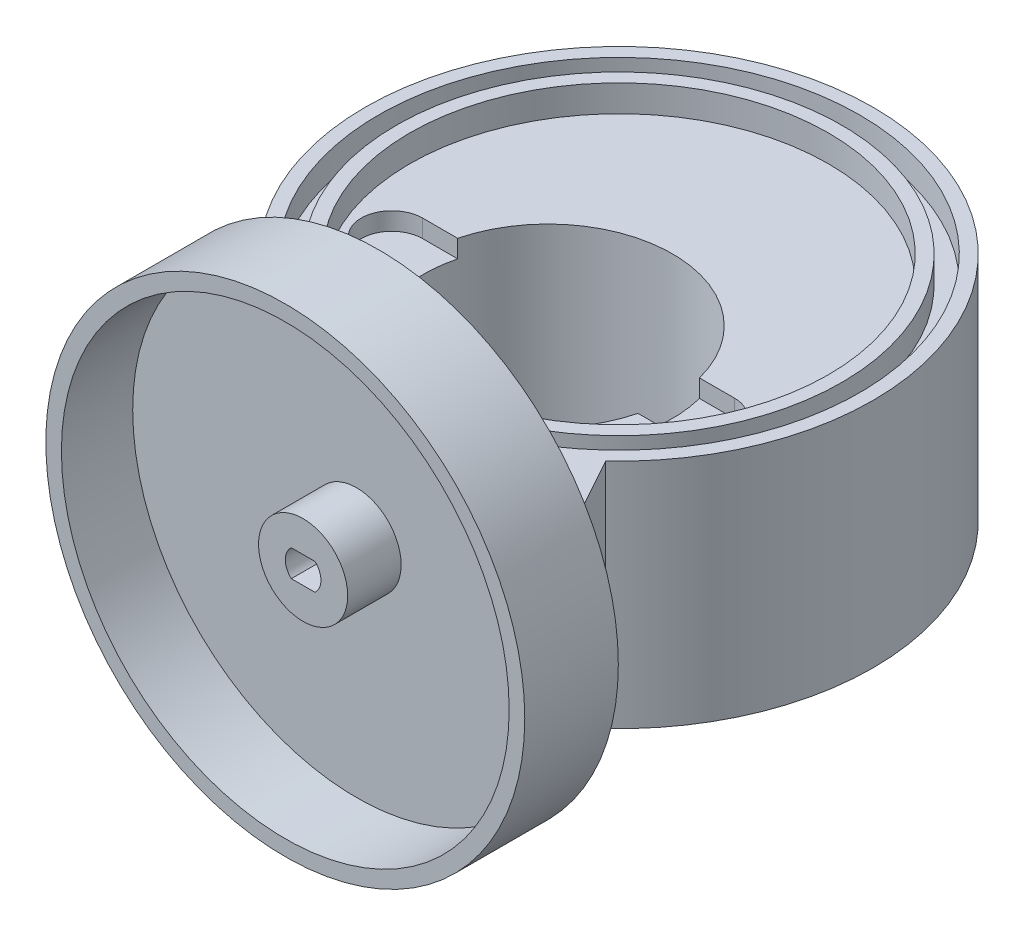
SolidWorks part; units mm, degrees
material "Custom Plastic"
ref_plane "Front Plane" through (0, 0, 0) normal (0, 0, 1) x (1, 0, 0)
ref_plane "Top Plane" through (0, 0, 0) normal (0, 1, 0) x (1, 0, 0)
ref_plane "Right Plane" through (0, 0, 0) normal (1, 0, 0) x (0, 0, -1)
sketch "Sketch1" plane through (0, 0, 0) normal (0, 1, 0) x (1, 0, 0)
  circle A0 centre (0, 0) radius 28.5
  dimension "D1" = 57
extrude "Boss-Extrude1" add sketch "Sketch1" along normal blind 3
sketch "Sketch2" plane through (0, 3, 0) normal (0, 1, 0) x (1, 0, 0)
  line L11 (0, 0) -> (0, -8) construction
  line L16 (-9, -18.7238) -> (-9, -20.2238)
  line L17 (-9, -20.2238) -> (-7.35, -22)
  line L18 (-7.35, -22) -> (-7.6173, -27.4632)
  line L20 (7.6173, -27.4632) -> (7.35, -22)
  line L21 (7.35, -22) -> (9, -20.2238)
  line L22 (9, -20.2238) -> (9, -18.7238)
  circle A9 centre (0, 0) radius 28.5 construction
  arc A10 (9, -18.7238) -> (13.5683, -11.45) centre (0, -8) ccw
  arc A12 (13.5683, -4.55) -> (-13.5683, -4.55) centre (0, -8) ccw
  arc A14 (-13.5683, -11.45) -> (-9, -18.7238) centre (0, -8) ccw
  arc A16 (-13.5683, -4.55) -> (-13.5683, -11.45) centre (0, -8) ccw
  arc A17 (13.5683, -4.55) -> (13.5683, -11.45) centre (0, -8) cw
  circle A18 centre (0, 0) radius 28.5
  circle M19 centre (0, 0) radius 28.5
  dimension "D2" = 57
  dimension "D1" = 8
extrude "Boss-Extrude4" add sketch "Sketch2" along normal blind 20 contours A12 A17 A10 L22 L21 L20 L18 L17 L16 A14 A16 M19 region at (-9.7988, 3, 19.4738)
sketch "Sketch5" plane through (0, 23, 0) normal (0, 1, 0) x (1, 0, 0)
  circle A0 centre (0, 0) radius 28.5
  circle A1 centre (0, 0) radius 23.5
  circle A2 centre (0, 0) radius 25
  circle A3 centre (0, 0) radius 27
  line M3 (9, -20.2238) -> (7.35, -22)
  line M4 (7.35, -22) -> (7.6173, -27.4632)
  arc M5 (7.6173, -27.4632) -> (-7.6173, -27.4632) centre (0, 0) ccw
  line M6 (-7.6173, -27.4632) -> (-7.35, -22)
  line M7 (-7.35, -22) -> (-9, -20.2238)
  dimension "D1" = 47
  dimension "D2" = 57
  dimension "D3" = 50
  dimension "D4" = 54
extrude "Boss-Extrude7" add sketch "Sketch5" along normal blind 3 contours A2 A1 M4 M6 M7 M3 | A3 M4 M5 M6 region at (22.0505, 23, 16.767) region at (-14.4007, 23, -19.5743)
sketch "Sketch7" plane through (0, 0, 0) normal (0, -1, 0) x (1, 0, 0)
  circle A0 centre (0, 0) radius 28.5
  circle A1 centre (0, 0) radius 23.5
  circle A2 centre (0, 0) radius 25
  circle A3 centre (0, 0) radius 27
extrude "Cut-Extrude1" cut sketch "Sketch7" against normal blind 3 contours A3 A2 region at (-26.2363, 0, 0)
sketch "Sketch8" plane through (0, 3, 0) normal (0, 1, 0) x (1, 0, 0)
  line L6 (-7.542, -25.9252) -> (-7.6173, -27.4632)
  line L7 (7.6173, -27.4632) -> (7.542, -25.9252)
  line L8 (-7.542, -25.9252) -> (-7.6173, -27.4632)
  line L9 (7.6173, -27.4632) -> (7.542, -25.9252)
  arc A2 (-7.542, -25.9252) -> (7.542, -25.9252) centre (0, 0) ccw
  arc A3 (-7.6173, -27.4632) -> (7.6173, -27.4632) centre (0, 0) ccw
  arc A4 (-7.542, -25.9252) -> (7.542, -25.9252) centre (0, 0) ccw
  arc A5 (-7.6173, -27.4632) -> (7.6173, -27.4632) centre (0, 0) ccw
  dimension "D1" = 0
extrude "Cut-Extrude2" cut sketch "Sketch8" against normal blind 5
sketch "Sketch9" plane through (0, 3, 0) normal (0, 1, 0) x (1, 0, 0)
  line L6 (-7.35, -22) -> (-7.4413, -23.8669)
  line L7 (7.4413, -23.8669) -> (7.35, -22)
  line L8 (7.35, -22) -> (9, -20.2238)
  line L9 (9, -20.2238) -> (9, -18.7238)
  line L10 (-9, -18.7238) -> (-9, -20.2238)
  line L11 (-9, -20.2238) -> (-7.35, -22)
  line L12 (-7.35, -22) -> (-7.4413, -23.8669)
  line L13 (7.4413, -23.8669) -> (7.35, -22)
  line L14 (7.35, -22) -> (9, -20.2238)
  line L15 (9, -20.2238) -> (9, -18.7238)
  line L16 (-9, -18.7238) -> (-9, -20.2238)
  line L17 (-9, -20.2238) -> (-7.35, -22)
  arc A2 (-7.4413, -23.8669) -> (7.4413, -23.8669) centre (0, 0) ccw
  arc A3 (9, -18.7238) -> (-9, -18.7238) centre (0, -8) ccw
  arc A4 (-7.4413, -23.8669) -> (7.4413, -23.8669) centre (0, 0) ccw
  arc A5 (9, -18.7238) -> (-9, -18.7238) centre (0, -8) ccw
  dimension "D1" = 0
extrude "Cut-Extrude3" cut sketch "Sketch9" against normal blind 5
ref_plane "Plane1" through (0, 0, 27.4632) normal (0, 0, 1) x (1, 0, 0)
sketch "Sketch10" plane through (0, 0, 27.4632) normal (0, 0, 1) x (1, 0, 0)
  line L0 (0, 26) -> (0, 0) construction
  line L1 (23.5, 26) -> (-23.5, 26) construction
  circle A0 centre (0, 13) radius 26.875
  dimension "D1" = 53.75
extrude "Boss-Extrude8" add sketch "Sketch10" along normal blind 2 and the other way blind 0.5
chamfer "Chamfer1" distance 12 angle 100 2 edges at (-9.2323, 13, 26.9632) (9.2323, 13, 26.9632) first distance on face at (0, 13, -0.7684)
sketch "Sketch11" plane through (0, 0, 29.4632) normal (0, 0, 1) x (1, 0, 0)
  circle A0 centre (0, 13) radius 26.875
  circle A1 centre (0, 13) radius 25.125
  dimension "D1" = 50.25
  dimension "D2" = 53.75
extrude "Boss-Extrude9" add sketch "Sketch11" along normal blind 8
sketch "Sketch12" plane through (0, 0, 29.4632) normal (0, 0, 1) x (1, 0, 0)
  circle A0 centre (0, 13) radius 5
  dimension "D1" = 10
sketch "Sketch13" plane through (0, 23, 0) normal (0, 1, 0) x (1, 0, 0)
  line L0 (13.5683, -11.45) -> (17.5, -11.45)
  line L1 (17.5, -4.55) -> (13.5683, -4.55)
  line L2 (-13.5683, -4.55) -> (-17.5, -4.55)
  line L3 (-17.5, -11.45) -> (-13.5683, -11.45)
  line L4 (-9, -18.7238) -> (-9, -20.2238)
  line L5 (-9, -20.2238) -> (-7.35, -22)
  line L6 (-7.35, -22) -> (-7.35, -25)
  line L7 (-7.35, -25) -> (7.35, -25)
  line L8 (7.35, -25) -> (7.35, -22)
  line L9 (7.35, -22) -> (9, -20.2238)
  line L10 (9, -20.2238) -> (9, -18.7238)
  arc A0 (9, -18.7238) -> (13.5683, -11.45) centre (0, -8) ccw
  arc A1 (17.5, -11.45) -> (17.5, -4.55) centre (17.5, -8) ccw
  arc A2 (13.5683, -4.55) -> (-13.5683, -4.55) centre (0, -8) ccw
  arc A3 (-17.5, -4.55) -> (-17.5, -11.45) centre (-17.5, -8) ccw
  arc A4 (-13.5683, -11.45) -> (-9, -18.7238) centre (0, -8) ccw
extrude "Cut-Extrude4" cut sketch "Sketch13" against normal blind 2
extrude "Boss-Extrude10" add sketch "Sketch12" along normal blind 6 contours A0
sketch "Sketch14" plane through (0, 0, 35.4632) normal (0, 0, 1) x (1, 0, 0)
  line L0 (-1.3229, 11.5) -> (1.3229, 11.5)
  line L1 (-1.3229, 14.5) -> (1.3229, 14.5)
  line L2 (0, 14.5) -> (0, 11.5) construction
  arc A0 (-1.3229, 14.5) -> (-1.3229, 11.5) centre (0, 13) ccw
  arc A1 (1.3229, 11.5) -> (1.3229, 14.5) centre (0, 13) ccw
  dimension "D1" = 4
  dimension "D2" = 3
extrude "Cut-Extrude5" cut sketch "Sketch14" against normal blind 6
